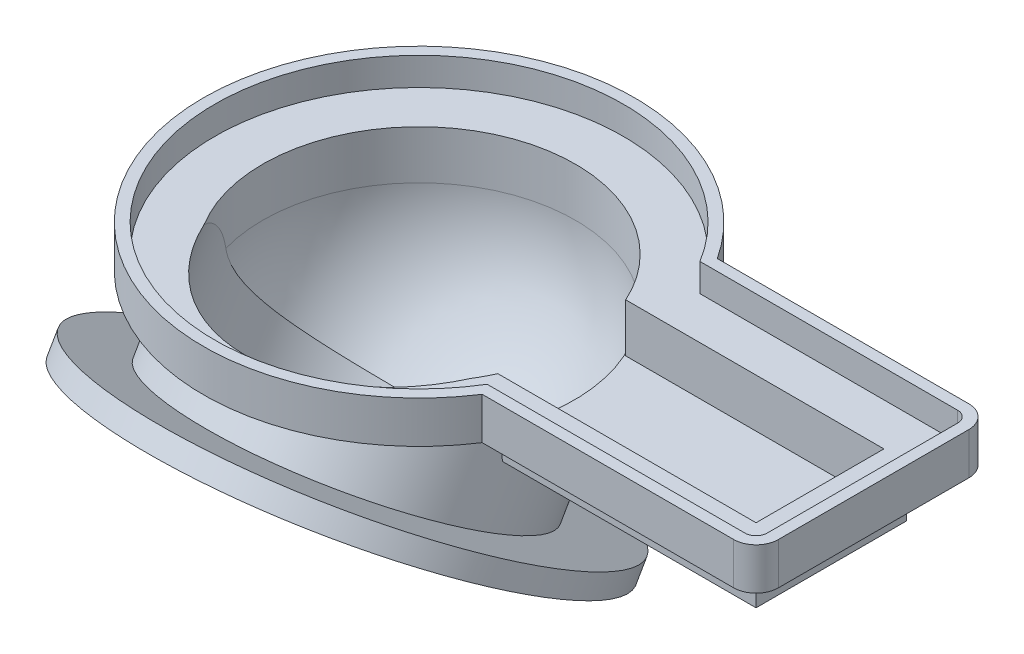
SolidWorks part; units mm, degrees
ref_plane "Front Plane" through (0, 0, 0) normal (0, 0, 1) x (1, 0, 0)
ref_plane "Top Plane" through (0, 0, 0) normal (0, 1, 0) x (1, 0, 0)
ref_plane "Right Plane" through (0, 0, 0) normal (1, 0, 0) x (0, 0, -1)
sketch "Sketch1" plane through (0, 0, 0) normal (0, 1, 0) x (1, 0, 0)
  line L0 (32.4497, -14.544) -> (91.186, -14.544)
  line L1 (91.186, 14.544) -> (32.4497, 14.544)
  line L2 (91.186, -14.544) -> (91.186, 14.544)
  line L3 (39.2577, -23.434) -> (100.076, -23.434) construction
  line L4 (100.076, -23.434) -> (100.076, 23.434) construction
  line L5 (100.076, 23.434) -> (39.2577, 23.434) construction
  line L6 (39.6879, -24.196) -> (100.838, -24.196)
  line L7 (100.838, -24.196) -> (100.838, 24.196)
  line L8 (100.838, 24.196) -> (39.6879, 24.196)
  arc A0 (32.4497, 14.544) -> (32.4497, -14.544) centre (0, 0) ccw
  arc A1 (39.2577, 23.434) -> (39.2577, -23.434) centre (0, 0) ccw construction
  arc A2 (39.6879, 24.196) -> (39.6879, -24.196) centre (0, 0) ccw
  dimension "D1" = 0.762
extrude "Boss-Extrude1" add sketch "Sketch1" along normal blind 3.175
ref_plane "Plane2" through (0, -20.307, 35.5403) normal (0, 0.8662, -0.4997) x (1, 0, 0)
sketch "Sketch3" plane through (0, -20.307, 35.5403) normal (0, 0.8662, -0.4997) x (1, 0, 0)
  circle A0 centre (0, 19.05) radius 36.8619
sketch "Sketch4" plane through (0, 0, 0) normal (0, -1, 0) x (1, 0, 0)
  line L3 (91.186, -14.544) -> (32.4497, -14.544)
  line L4 (91.186, 14.544) -> (91.186, -14.544)
  line L5 (32.4497, 14.544) -> (91.186, 14.544)
  arc A1 (32.4497, 14.544) -> (32.4497, -14.544) centre (0, 0) ccw
extrude "Extrude-Thin1" add sketch "Sketch4" along normal blind 7.874 thin thin type one direction wall 2.54
ref_axis "Axis1" through (0, -50.8185, 0) along (0, 1, 0)
sketch "Sketch5" plane through (0, 0, 0) normal (0, 0, 1) x (1, 0, 0)
  line L0 (0, -50.8185) -> (0, 5.7461) construction
  line L1 (-38.1, -7.874) -> (34.055, -7.874) construction
  line L2 (-35.56, -7.874) -> (32.4497, -7.874) construction
  line L3 (0, -43.434) -> (0, -45.974)
  line L4 (-38.1, -7.874) -> (-35.56, -7.874)
  arc A0 (-38.1, -7.874) -> (0, -45.974) centre (0, -7.874) ccw
  arc A1 (-35.56, -7.874) -> (0, -43.434) centre (0, -7.874) ccw
revolve "Revolve1" add sketch "Sketch5" angle 360 about axis through (0, -50.8185, 0) along (0, 1, 0)
sketch "Sketch6" plane through (0, -7.874, 0) normal (0, -1, 0) x (1, 0, 0)
  line L0 (34.055, -17.084) -> (93.726, -17.084) construction
  line L1 (93.726, 17.084) -> (34.055, 17.084) construction
  line L2 (93.726, -17.084) -> (93.726, 17.084) construction
  line L9 (30.8894, -17.084) -> (93.726, -17.084)
  line L10 (93.726, -17.084) -> (93.726, 17.084)
  line L11 (93.726, 17.084) -> (30.8894, 17.084)
  arc A2 (30.8894, -17.084) -> (30.8894, 17.084) centre (0, 0) ccw
  dimension "D1" = 70.5979
extrude "Boss-Extrude2" add sketch "Sketch6" along normal blind 3.175
sketch "Sketch7" plane through (0, -20.307, 35.5403) normal (0, 0.8662, -0.4997) x (1, 0, 0)
  circle A0 centre (0, 19.05) radius 36.8619 construction
  circle A1 centre (0, 19.05) radius 36.8619
extrude "Extrude-Thin2" add sketch "Sketch7" along normal up to body separate body thin thin type one direction reverse wall 2.54
sketch "Sketch8" plane through (0, -20.307, 35.5403) normal (0, 0.8662, -0.4997) x (1, 0, 0)
  circle A0 centre (0, 19.05) radius 34.3219 construction
  circle A1 centre (0, 19.05) radius 34.3219
extrude "Cut-Extrude1" cut sketch "Sketch8" against normal blind 13.335 and the other way blind 44.45
sketch "Sketch10" plane through (0, -30.6195, 17.6651) normal (0, -0.8662, 0.4997) x (1, 0, 0)
  circle A0 centre (0, 0) radius 50.8
  circle A1 centre (0, 1.5866) radius 34.3219 construction
  circle A2 centre (0, 1.5866) radius 34.3219
  dimension "D1" = 101.6
extrude "Boss-Extrude3" add sketch "Sketch10" against normal blind 5.08
fillet "Fillet1" radius 2.54 2 edges at (100.838, 1.5875, 24.196) (100.838, 1.5875, -24.196)
sketch "Sketch11" plane through (0, 3.175, 0) normal (0, 1, 0) x (1, 0, 0)
  line L0 (41.0894, -26.736) -> (98.298, -26.736)
  line L1 (103.378, -21.656) -> (103.378, 21.656)
  line L2 (98.298, 26.736) -> (41.0894, 26.736)
  line L3 (39.6879, -24.196) -> (98.298, -24.196)
  line L4 (100.838, -21.656) -> (100.838, 21.656)
  line L5 (98.298, 24.196) -> (39.6879, 24.196)
  line L6 (39.6879, -24.196) -> (98.298, -24.196)
  line L7 (100.838, -21.656) -> (100.838, 21.656)
  line L8 (98.298, 24.196) -> (39.6879, 24.196)
  arc A0 (41.0894, 26.736) -> (41.0894, -26.736) centre (0, 0) ccw
  arc A1 (98.298, -26.736) -> (103.378, -21.656) centre (98.298, -21.656) ccw
  arc A2 (103.378, 21.656) -> (98.298, 26.736) centre (98.298, 21.656) ccw
  arc A3 (98.298, -24.196) -> (100.838, -21.656) centre (98.298, -21.656) ccw
  arc A4 (100.838, 21.656) -> (98.298, 24.196) centre (98.298, 21.656) ccw
  arc A5 (39.6879, 24.196) -> (39.6879, -24.196) centre (0, 0) ccw
  arc A6 (98.298, -24.196) -> (100.838, -21.656) centre (98.298, -21.656) ccw
  arc A7 (100.838, 21.656) -> (98.298, 24.196) centre (98.298, 21.656) ccw
  arc A8 (39.6879, 24.196) -> (39.6879, -24.196) centre (0, 0) ccw
  dimension "D1" = 0
  dimension "D2" = 2.54
extrude "Boss-Extrude4" add sketch "Sketch11" along normal blind 6.35 and the other way up to surface (3.175 mm away) other way up to face at (40.9374, 0, 1.9539)
